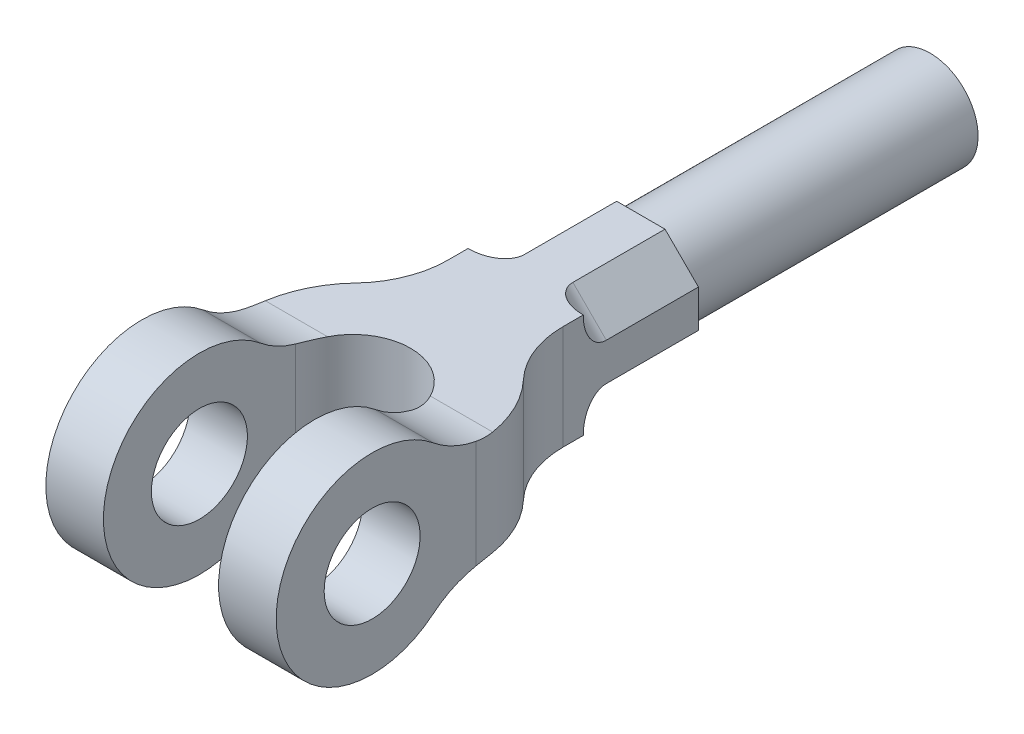
SolidWorks part; units mm, degrees
ref_plane "Front Plane" through (0, 0, 0) normal (0, 0, 1) x (1, 0, 0)
ref_plane "Top Plane" through (0, 0, 0) normal (0, 1, 0) x (1, 0, 0)
ref_plane "Right Plane" through (0, 0, 0) normal (1, 0, 0) x (0, 0, -1)
sketch "Sketch1" plane through (0, 0, 0) normal (0, 1, 0) x (1, 0, 0)
  line L1 (-542.576, 1296.9589) -> (657.424, 1296.9589)
  line L2 (-542.576, 1296.9589) -> (-542.576, -1203.0411)
  line L3 (-542.576, -1203.0411) -> (657.424, -1203.0411)
  line L4 (657.424, 1296.9589) -> (657.424, -1203.0411)
  dimension "D1" = 2500
  dimension "D2" = 1200
extrude "Boss-Extrude1" add sketch "Sketch1" along normal blind 1000 contours L2 L1 L4 L3
sketch "Sketch2" plane through (0, 1000, 0) normal (0, 1, 0) x (1, 0, 0)
  line L0 (57.424, 1296.9589) -> (57.424, -1203.0411) construction
  line L1 (-542.576, 1296.9589) -> (657.424, 1296.9589) construction
  line L2 (-542.576, -1203.0411) -> (657.424, -1203.0411) construction
  line L3 (-242.576, 591.9423) -> (-242.576, 1296.9589)
  line L4 (357.424, 591.9423) -> (357.424, 1296.9589)
  line L5 (-242.576, -203.0411) -> (-242.576, -1203.0411)
  line L6 (357.424, -203.0411) -> (357.424, -1203.0411)
  line L9 (-542.576, -1203.0411) -> (657.424, -1203.0411)
  line L10 (657.424, -1203.0411) -> (657.424, 1296.9589)
  line L11 (657.424, 1296.9589) -> (-542.576, 1296.9589)
  line L12 (-542.576, 1296.9589) -> (-542.576, -1203.0411)
  line L13 (-542.576, -1203.0411) -> (657.424, -1203.0411)
  line L14 (657.424, -1203.0411) -> (657.424, 1296.9589)
  line L15 (657.424, 1296.9589) -> (-542.576, 1296.9589)
  line L16 (-542.576, 1296.9589) -> (-542.576, -1203.0411)
  arc A0 (357.424, -203.0411) -> (-242.576, -203.0411) centre (57.424, -203.0411) ccw
  arc A1 (-378.9397, 248.768) -> (493.7876, 248.768) centre (57.424, -163.0411) ccw
  arc A2 (-242.576, 591.9423) -> (-378.9397, 248.768) centre (-742.576, 591.9423) cw
  arc A3 (357.424, 591.9423) -> (493.7876, 248.768) centre (857.424, 591.9423) ccw
  point P28 (-242.576, 356.5741)
  point P31 (357.424, 356.5741)
  line M11 (-542.576, -1203.0411) -> (657.424, -1203.0411)
  line M13 (657.424, 1296.9589) -> (-542.576, 1296.9589)
  line M14 (-542.576, 1296.9589) -> (-542.576, -1203.0411)
  dimension "D1" = 1200
  dimension "D2" = 600
  dimension "D4" = 1500
  dimension "D7" = 500
  dimension "D3" = 40
  dimension "D5" = 300
  dimension "D6" = 0
extrude "Cut-Extrude1" cut sketch "Sketch2" against normal blind 1000 contours A2 L3 A1 M13 M14 | L4 A3 A1 L14 M13 | A1 L0 L13 L6 | L0 A1 L5 M11 | L0 A0 L5 A1 | A0 L0 A1 L6 region at (197.9091, 1000, 349.6671) region at (-83.0611, 1000, 349.6671) region at (519.1721, 1000, -751.9858) region at (-404.3241, 1000, -751.9858) region at (211.6718, 1000, 969.4216) region at (-96.8238, 1000, 969.4216)
sketch "Sketch3" plane through (657.424, 0, 0) normal (1, 0, 0) x (0, 0, -1)
  line L0 (-1203.0411, 1000) -> (-1203.0411, 0) construction
  line L1 (-163.0411, 0) -> (-1203.0411, 0) construction
  line L2 (-163.0411, 1000) -> (-1203.0411, 1000) construction
  line L3 (-703.0411, 500) -> (1296.9589, 500) construction
  line L4 (1296.9589, 0) -> (1296.9589, 1000) construction
  line L5 (1296.9589, 0) -> (1296.9589, 1000) construction
  line L6 (-67.3604, 771.952) -> (1296.9589, 771.952)
  line L8 (-67.3604, 228.048) -> (1296.9589, 228.048)
  line L9 (1296.9589, 771.952) -> (1296.9589, 228.048)
  line L10 (-163.0411, 0) -> (248.768, 0) construction
  line L11 (248.768, 0) -> (591.9423, 0) construction
  line L12 (591.9423, 0) -> (1296.9589, 0) construction
  line L13 (591.9423, 1000) -> (1296.9589, 1000) construction
  line L14 (591.9423, 1000) -> (248.768, 1000) construction
  line L15 (248.768, 1000) -> (-163.0411, 1000) construction
  line L16 (1296.9589, 0) -> (1296.9589, 1000)
  line L17 (1296.9589, 0) -> (1296.9589, 1000)
  line L18 (-163.0411, 0) -> (-1203.0411, 0)
  line L19 (-163.0411, 0) -> (248.768, 0)
  line L20 (248.768, 0) -> (591.9423, 0)
  line L21 (591.9423, 0) -> (1296.9589, 0)
  line L22 (591.9423, 1000) -> (1296.9589, 1000)
  line L23 (591.9423, 1000) -> (248.768, 1000)
  line L24 (248.768, 1000) -> (-163.0411, 1000)
  line L25 (-163.0411, 1000) -> (-1203.0411, 1000)
  line L26 (-1203.0411, 1000) -> (-1203.0411, 0)
  arc A0 (-385.2008, 885.976) -> (-385.2008, 114.024) centre (-703.0411, 500) ccw
  circle A1 centre (-703.0411, 500) radius 250
  arc A2 (-385.2008, 114.024) -> (-67.3604, 228.048) centre (-67.3604, -271.952) cw
  arc A3 (-67.3604, 771.952) -> (-385.2008, 885.976) centre (-67.3604, 1271.952) cw
  line M8 (-1203.0411, 0) -> (-163.0411, 0)
  line M9 (-163.0411, 0) -> (-163.0411, 1000)
  line M10 (-163.0411, 1000) -> (-1203.0411, 1000)
  line M11 (-1203.0411, 1000) -> (-1203.0411, 0)
  dimension "D1" = 500
  dimension "D2" = 500
extrude "Cut-Extrude5" cut sketch "Sketch3" against normal blind 1200 and the other way through all contours A0 L25 M11 | A0 L26 M8 | A1 | A2 A0 L18 M9 | A3 A0 M9 M10 | A3 L6 L16 L22 L23 L24 M9 | A2 L19 L20 L21 L16 L8 M9 region at (657.424, 886.0742, -567.5821) region at (657.424, 921.6221, 308.2467) region at (657.424, 113.9258, -567.5821) region at (657.424, 78.3779, 308.2467) region at (657.424, 888.316, 1091.3572) region at (657.424, 111.684, 1091.3572) region at (657.424, 500, 703.0411)
sketch "Sketch4" plane through (0, 0, -1296.9589) normal (0, 0, -1) x (-1, 0, 0)
  line L0 (242.576, 771.952) -> (-357.424, 228.048) construction
  line L1 (68.576, 771.952) -> (242.576, 771.952)
  line L2 (242.576, 771.952) -> (-357.424, 771.952) construction
  line L3 (242.576, 771.952) -> (242.576, 597.952)
  line L4 (242.576, 228.048) -> (242.576, 771.952) construction
  line L5 (242.576, 597.952) -> (68.576, 771.952)
  line L6 (-357.424, 771.952) -> (-357.424, 597.952)
  line L7 (-357.424, 228.048) -> (-357.424, 771.952) construction
  line L8 (-357.424, 597.952) -> (-183.424, 771.952)
  line L9 (-183.424, 771.952) -> (-357.424, 771.952)
  line L10 (242.576, 228.048) -> (242.576, 402.048)
  line L11 (68.576, 228.048) -> (242.576, 228.048)
  line L12 (242.576, 402.048) -> (68.576, 228.048)
  line L13 (-183.424, 228.048) -> (-357.424, 228.048)
  line L14 (-357.424, 228.048) -> (-357.424, 402.048)
  line L15 (-357.424, 402.048) -> (-183.424, 228.048)
  circle A0 centre (-57.424, 500) radius 250
  point P24 (-57.424, 500)
  point P28 (-57.424, 500)
  dimension "D1" = 500
  dimension "D2" = 174
  dimension "D3" = 174
  dimension "D4" = 174
  dimension "D5" = 174
  dimension "D6" = 2
  dimension "D7" = 2
extrude "Cut-Extrude6" cut sketch "Sketch4" against normal blind 600 contours L9 L6 L8 | L5 L1 L3 | L10 L12 L11 | L13 L14 L15
extrude "Boss-Extrude2" add sketch "Sketch4<3>" along normal blind 1507 contours A0 L0 | L0 A0 region at (-13.8375, 421.3889, -1296.9589) region at (128.6855, 578.6111, -1296.9589)
sketch "Sketch4<3>" plane through (0, 0, -1296.9589) normal (0, 0, -1) x (-1, 0, 0) same geometry as "Sketch4"
fillet "Fillet1" radius 120 4 edges at (270.424, 315.048, -696.9589) (270.424, 684.952, -696.9589) (-155.576, 315.048, -696.9589) (-155.576, 684.952, -696.9589)
